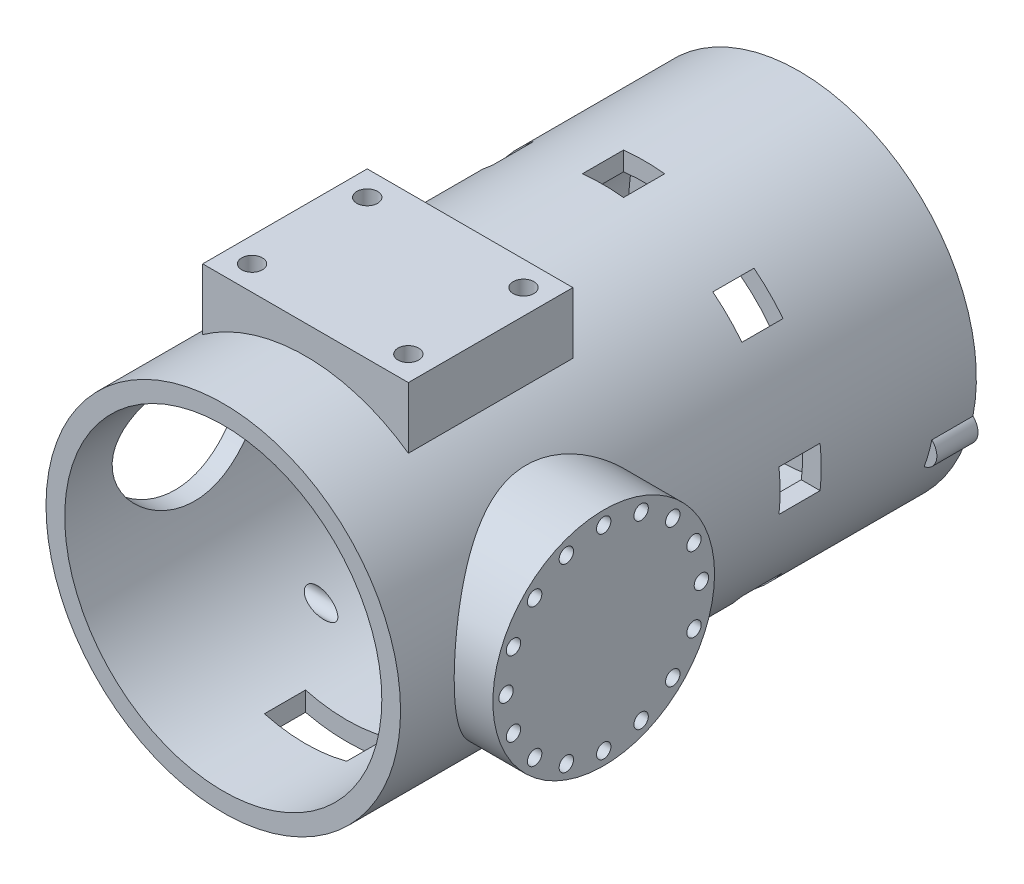
SolidWorks part; units mm, degrees
other "Markup1"
sketch "Sketch14" plane through (-43.1, 43.1, 140) normal (-0.1765, 0.0048, 0.9843) x (0.9842, -0.0149, 0.1765)
other "Markup2"
sketch "Sketch23" plane through (45.1, -43.1, 140) normal (0.9491, -0.0629, 0.3087) x (0.311, 0.031, -0.9499)
ref_plane "Front Plane" through (0, 0, 0) normal (0, 0, 1) x (1, 0, 0)
ref_plane "Top Plane" through (0, 0, 0) normal (0, 1, 0) x (1, 0, 0)
ref_plane "Right Plane" through (0, 0, 0) normal (1, 0, 0) x (0, 0, -1)
sketch "Sketch1" plane through (0, 0, 0) normal (0, 0, 1) x (1, 0, 0)
  circle A1 centre (0, 0) radius 43.1
  dimension "D1" = 86.2
extrude "Main Body" add sketch "Sketch1" along normal blind 140
ref_plane "Plane1" through (0, 43.1, 0) normal (0, 1, 0) x (1, 0, 0)
sketch "Sketch34" [suppressed] plane through (0, 43.1, 0) normal (0, 1, 0) x (1, 0, 0)
  line L6 (-5, -13) -> (5, -13)
  line L8 (-5, -13) -> (-5, -3)
  line L9 (-5, -3) -> (5, -3)
  line L10 (5, -13) -> (5, -3)
  line L11 (-5, -13) -> (5, -3) construction
  line L12 (-5, -3) -> (5, -13) construction
  point P0 (0, -8)
  dimension "D1" = 8
  dimension "D2" = 10
  dimension "D3" = 10
sketch "Sketch6" plane through (0, 43.1, 0) normal (0, 1, 0) x (1, 0, 0)
  line L2 (-5, -47.7) -> (5, -47.7)
  line L3 (-5, -47.7) -> (-5, -37.7)
  line L4 (-5, -37.7) -> (5, -37.7)
  line L5 (5, -47.7) -> (5, -37.7)
  line L6 (-5, -47.7) -> (5, -37.7) construction
  line L7 (-5, -37.7) -> (5, -47.7) construction
  point P2 (0, -42.7)
  dimension "D2" = 10
  dimension "D1" = 42.7
  dimension "D3" = 10
extrude "Cut-Extrude3" cut sketch "Sketch6" against normal through all
pattern_circular "Rotated Plug Pattern" count 4 every 45 about axis through (0, 0, 140) along (0, 0, 1) of "Cut-Extrude3"
ref_plane "Plane2" through (52.5, 0, 0) normal (1, 0, 0) x (0, 0, -1)
sketch "Sketch8" plane through (52.5, 0, 0) normal (1, 0, 0) x (0, 0, -1)
  circle A0 centre (-100, 0) radius 26.95
  dimension "D1" = 53.9
  dimension "D2" = 100
extrude "Boss-Extrude2" add sketch "Sketch8" against normal blind 20
mirror "Mirror1" [suppressed] about plane through (0, 0, 0) normal (1, 0, 0)
ref_plane "Plane3" through (0, 50, 0) normal (0, 1, 0) x (1, 0, 0)
sketch "Sketch33" plane through (0, 50, 0) normal (0, 1, 0) x (1, 0, 0)
  line L1 (-25, -120) -> (25, -120)
  line L2 (-25, -120) -> (-25, -80)
  line L3 (-25, -80) -> (25, -80)
  line L4 (25, -120) -> (25, -80)
  line L5 (-25, -120) -> (25, -80) construction
  line L6 (-25, -80) -> (25, -120) construction
  point P0 (0, -100)
  dimension "D1" = 100
  dimension "D2" = 40
  dimension "D3" = 50
extrude "Boss-Extrude11" add sketch "Sketch33" against normal blind 22
sketch "Sketch35" plane through (0, 50, 0) normal (0, 1, 0) x (1, 0, 0)
  line L0 (-25, -120) -> (-25, -80) construction
  line L1 (25, -120) -> (25, -80) construction
  line L2 (25, -80) -> (-25, -80) construction
  line L3 (-25, -120) -> (25, -120) construction
  circle A0 centre (-19, -86) radius 2.525
  circle A1 centre (19, -86) radius 2.525
  circle A2 centre (-19, -114) radius 2.525
  circle A3 centre (19, -114) radius 2.525
  dimension "D1" = 5.05
  dimension "D2" = 6
  dimension "D3" = 6
  dimension "D4" = 6
  dimension "D5" = 6
extrude "Cut-Extrude14" cut sketch "Sketch35" against normal blind 4
sketch "Sketch5" plane through (0, 0, 140) normal (0, 0, 1) x (1, 0, 0)
  circle A0 centre (0, 0) radius 32
  dimension "D1" = 64
extrude "Hole 1" cut sketch "Sketch5" against normal through all
sketch "Sketch10" plane through (0, 0, 0) normal (0, 1, 0) x (1, 0, 0)
  line L0 (43.1, 0) -> (-43.1, 0) construction
  line L1 (-10, -120) -> (10, -120)
  line L2 (-10, -120) -> (-10, -110)
  line L3 (-10, -110) -> (10, -110)
  line L4 (10, -120) -> (10, -110)
  line L5 (-10, -120) -> (10, -110) construction
  line L6 (-10, -110) -> (10, -120) construction
  point P0 (0, -115)
  point P7 (-10, -115)
  dimension "D1" = 110
  dimension "D2" = 10
  dimension "D3" = 20
extrude "Motor Wire Hole" cut sketch "Sketch10" against normal through all
sketch "Sketch27" plane through (0, 0, 0) normal (1, 0, 0) x (0, 0, -1)
  line L1 (-100, -36.5) -> (-60, -36.5)
  line L2 (-100, -36.5) -> (-100, -27.5)
  line L3 (-100, -27.5) -> (-60, -27.5)
  line L4 (-60, -36.5) -> (-60, -27.5)
  dimension "D1" = 60
  dimension "D2" = 27.5
  dimension "D3" = 40
  dimension "D4" = 9
extrude "Boss-Extrude9" add sketch "Sketch27" along normal blind 33 and the other way blind 33
sketch "Sketch11" plane through (0, 0, 0) normal (1, 0, 0) x (0, 0, -1)
  circle A0 centre (-65, -32) radius 2.25
  circle A1 centre (-95, -32) radius 2.25
  dimension "D3" = 4.5
  dimension "D1" = 65
  dimension "D2" = 32
  dimension "D4" = 30
extrude "Cut-Extrude6" cut sketch "Sketch11" against normal through all both and the other way through all
sketch "Sketch28" plane through (-33, 0, 0) normal (-1, 0, 0) x (0, 0, 1)
  line L0 (62.8927, -28.35) -> (67.1073, -28.35)
  line L1 (67.1073, -28.35) -> (69.2147, -32)
  line L2 (69.2147, -32) -> (67.1073, -35.65)
  line L3 (67.1073, -35.65) -> (62.8927, -35.65)
  line L4 (62.8927, -35.65) -> (60.7853, -32)
  line L6 (60.7853, -32) -> (62.8927, -28.35)
  line L7 (92.8927, -28.35) -> (97.1073, -28.35)
  line L8 (97.1073, -28.35) -> (99.2147, -32)
  line L9 (99.2147, -32) -> (97.1073, -35.65)
  line L10 (97.1073, -35.65) -> (92.8927, -35.65)
  line L11 (92.8927, -35.65) -> (90.7853, -32)
  line L12 (90.7853, -32) -> (92.8927, -28.35)
  circle A0 centre (65, -32) radius 3.65 construction
  circle A1 centre (65, -32) radius 2.25 construction
  circle A2 centre (95, -32) radius 3.65 construction
  circle A3 centre (95, -32) radius 2.25 construction
  dimension "D2" = 7.3
extrude "Cut-Extrude7" cut sketch "Sketch28" against normal blind 3
sketch "Sketch29" plane through (33, 0, 0) normal (1, 0, 0) x (0, 0, -1)
  circle A0 centre (-95, -32) radius 3.6
  circle A1 centre (-65, -32) radius 3.6
  dimension "D1" = 7.2
extrude "Cut-Extrude8" cut sketch "Sketch29" against normal blind 4
sketch "Sketch2" plane through (0, 0, 140) normal (0, 0, 1) x (1, 0, 0)
  circle A0 centre (0, 0) radius 38.55
  dimension "D1" = 77.1
extrude "Cut-Extrude5" cut sketch "Sketch2" against normal blind 135
sketch "Sketch9" plane through (0, 0, 5) normal (0, 0, 1) x (1, 0, 0)
  circle A0 centre (0, 0) radius 38.1
  circle A1 centre (0, 0) radius 36.44
  dimension "D1" = 76.2
  dimension "D2" = 1.66
extrude "Boss-Extrude3" add sketch "Sketch9" along normal blind 10
extrude "Cut-Extrude13" [suppressed] cut sketch "Sketch34" against normal blind 15
sketch "Sketch30" plane through (52.5, 0, 0) normal (1, 0, 0) x (0, 0, -1)
  line L0 (-100, 23.75) -> (-100, 0) construction
  circle A0 centre (-100, 0) radius 23.75 construction
  circle A1 centre (-100, 23.75) radius 1.75
  circle A2 centre (-90.9113, 21.9421) radius 1.75
  circle A3 centre (-83.2062, 16.7938) radius 1.75
  circle A4 centre (-78.0579, 9.0887) radius 1.75
  circle A5 centre (-76.25, 0) radius 1.75
  circle A6 centre (-78.0579, -9.0887) radius 1.75
  circle A7 centre (-83.2062, -16.7938) radius 1.75
  circle A8 centre (-90.9113, -21.9421) radius 1.75
  circle A9 centre (-100, -23.75) radius 1.75
  circle A10 centre (-109.0887, -21.9421) radius 1.75
  circle A11 centre (-116.7938, -16.7938) radius 1.75
  circle A12 centre (-121.9421, -9.0887) radius 1.75
  circle A13 centre (-123.75, 0) radius 1.75
  circle A14 centre (-121.9421, 9.0887) radius 1.75
  circle A15 centre (-116.7938, 16.7938) radius 1.75
  circle A16 centre (-109.0887, 21.9421) radius 1.75
  point P38 (-100, 0)
  dimension "D1" = 47.5
  dimension "D2" = 3.5
  dimension "D3" = 16
extrude "Cut-Extrude9" cut sketch "Sketch30" against normal up to surface (22.1349 mm away) up to face at (21.4947, -32.0013, 97.25)
sketch "Sketch31" plane through (52.5, 0, 0) normal (1, 0, 0) x (0, 0, -1)
  line L0 (0, -43.1) -> (0, 43.1) construction
  line L1 (0, -15) -> (-10, -15)
  line L2 (0, -15) -> (0, -7.5)
  line L3 (0, -7.5) -> (-10, -7.5)
  line L4 (-10, -15) -> (-10, -7.5)
  dimension "D1" = 15
  dimension "D2" = 7.5
  dimension "D3" = 10
extrude "Boss-Extrude10" add sketch "Sketch31" against normal up to body from offset 9 offset against normal yes
sketch "Sketch32" plane through (0, 0, 0) normal (0, 0, -1) x (-1, 0, 0)
  line L0 (-43.5, -11.25) -> (-29.9573, -11.25) construction
  line L1 (-43.5, -15) -> (-43.5, -7.5) construction
  line L3 (-42.4424, -7.5) -> (-43.5, -7.5) construction
  line L5 (-43.5, -15) -> (-43.5, -7.5)
  line L6 (-43.5, -7.5) -> (-42.4424, -7.5)
  circle A0 centre (0, 0) radius 32 construction
  arc A2 (-40.4056, -15) -> (-42.4424, -7.5) centre (0, 0) ccw construction
  arc A3 (-40.4056, -15) -> (-42.2658, -8.4385) centre (-39.6806, -11.25) cw
  arc A4 (-42.2658, -8.4385) -> (-42.4424, -7.5) centre (0, 0) cw
  line M3 (-42.4424, -7.5) -> (-43.5, -7.5)
  line M4 (-43.5, -7.5) -> (-43.5, -15)
  line M5 (-43.5, -15) -> (-40.4056, -15)
extrude "Cut-Extrude10" cut sketch "Sketch32" against normal up to surface (10 mm away) contours M4 M3 | L5 M5 region at (43.0347, -8.5479, 0) region at (42.7123, -14.1508, 0) up to face at (42.5043, -11.2615, 10)
ref_plane "Plane4" through (-43.1, 0, 0) normal (-1, 0, 0) x (0, 0, 1)
sketch "Sketch36" plane through (-43.1, 0, 0) normal (-1, 0, 0) x (0, 0, 1)
  line L0 (140, -43.1) -> (140, 43.1) construction
  line L1 (47.41, 43.1) -> (-47.41, 43.1) construction
  circle A0 centre (110, 8.1) radius 19.05
  dimension "D1" = 38.1
  dimension "D2" = 30
  dimension "D3" = 35
extrude "Cut-Extrude15" cut sketch "Sketch36" against normal up to next
